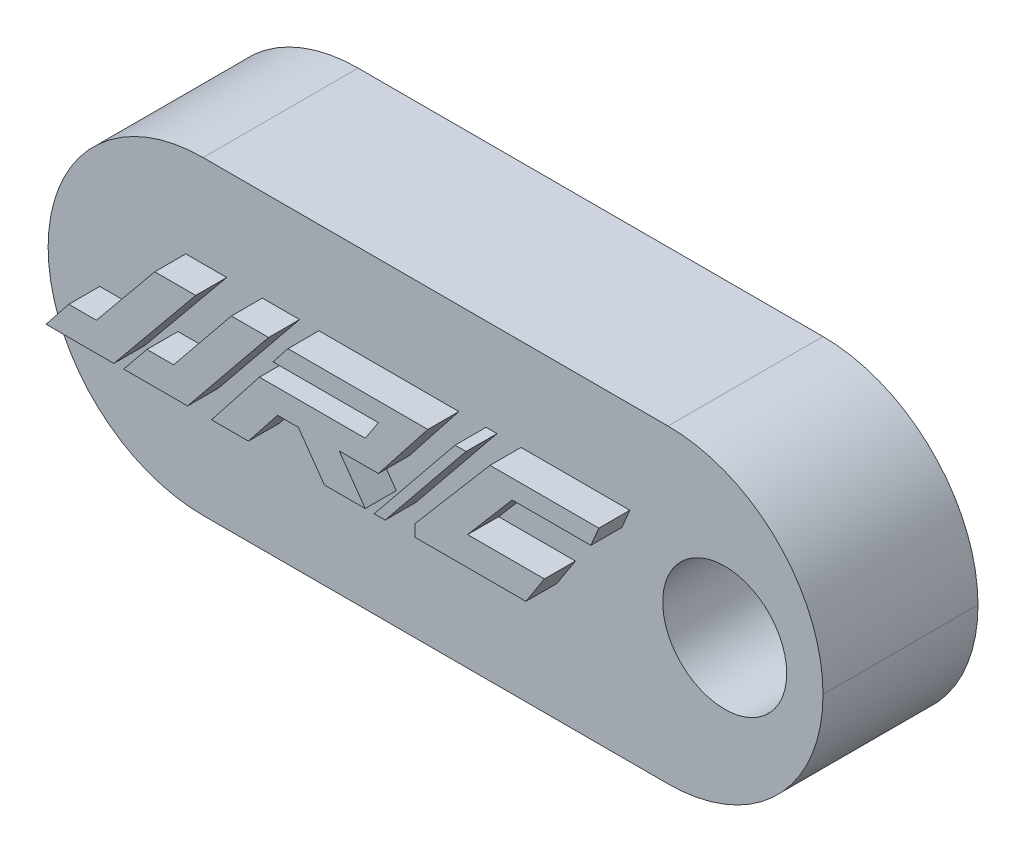
SolidWorks part; units mm, degrees
ref_plane "Plan de face" through (0, 0, 0) normal (0, 0, 1) x (1, 0, 0)
ref_plane "Plan de dessus" through (0, 0, 0) normal (0, 1, 0) x (1, 0, 0)
ref_plane "Plan de droite" through (0, 0, 0) normal (1, 0, 0) x (0, 0, -1)
sketch "Esquisse1" plane through (0, 0, 0) normal (0, 0, 1) x (1, 0, 0)
  line L1 (-25, -10) -> (25, -10)
  line L2 (-25, -10) -> (-25, 10)
  line L3 (-25, 10) -> (25, 10)
  line L4 (25, -10) -> (25, 10)
  line L5 (-25, -10) -> (25, 10) construction
  line L6 (-25, 10) -> (25, -10) construction
  point P0 (0, 0)
  dimension "D1" = 20
  dimension "D2" = 50
extrude "Boss.-Extru.1" add sketch "Esquisse1" along normal blind 10
fillet "Congé1" radius 10 4 edges at (-25, 10, 5) (25, 10, 5) (25, -10, 5) (-25, -10, 5)
sketch "Esquisse2" plane through (0, 0, 10) normal (0, 0, 1) x (1, 0, 0)
  circle A0 centre (18.6554, 0) radius 4
extrude "Enlèv. mat.-Extru.1" cut sketch "Esquisse2" against normal through all
sketch "Esquisse3" plane through (0, 0, 10) normal (0, 0, 1) x (1, 0, 0)
  line L0 (-23.1374, -2.3821) -> (-18.759, -2.3821)
  line L1 (-18.759, -2.3821) -> (-13.4772, 4.0591)
  line L2 (-13.4772, 4.0591) -> (-16.1181, 4.0591)
  line L3 (-16.1181, 4.0591) -> (-19.8842, -0.5337)
  line L4 (-19.8842, -0.5337) -> (-21.6692, -0.5337)
  line L5 (-21.6692, -0.5337) -> (-23.1374, -2.3821)
  line L6 (-18.1265, -2.3821) -> (-14.0041, -2.3821)
  line L7 (-14.0041, -2.3821) -> (-8.7745, 4.0591)
  line L8 (-18.1265, -2.3821) -> (-16.6258, -0.5337)
  line L9 (-16.6258, -0.5337) -> (-14.9059, -0.5337)
  line L10 (-14.9059, -0.5337) -> (-11.177, 4.0591)
  line L11 (-11.177, 4.0591) -> (-8.7745, 4.0591)
  line L12 (-12.4582, -2.3821) -> (-10.0749, -2.3821)
  line L13 (-12.4582, -2.3821) -> (-9.3664, 1.5471)
  line L14 (-9.3664, 1.5471) -> (-2.5386, 1.5471)
  line L15 (-10.0749, -2.3821) -> (-8.2005, 0)
  line L16 (-8.2005, 0) -> (-6.8543, 0)
  line L17 (-6.8543, 0) -> (-5.1732, -2.3821)
  line L18 (-5.1732, -2.3821) -> (-2.5386, -2.3821)
  line L19 (-2.5386, -2.3821) -> (-4.2197, 0)
  line L20 (-4.2197, 0) -> (-1.6914, 0)
  line L21 (-1.6914, 0) -> (1.5026, 4.0591)
  line L22 (1.5026, 4.0591) -> (-7.5274, 4.0591)
  line L23 (-7.5274, 4.0591) -> (-8.4872, 2.8394)
  line L24 (-8.4872, 2.8394) -> (-1.6914, 2.8394)
  line L25 (-1.6914, 2.8394) -> (-2.5386, 1.5471)
  line L26 (3.2585, 4.0591) -> (3.967, 4.0591)
  line L27 (3.967, 4.0591) -> (-1.2504, -2.3821)
  line L28 (3.2585, 4.0591) -> (-1.9589, -2.3821)
  line L29 (-1.9589, -2.3821) -> (-1.2504, -2.3821)
  line L30 (7.8318, -2.3821) -> (0.682, -2.3821)
  line L31 (0.682, -1.6092) -> (5.5129, 4.0591)
  line L32 (5.5129, 4.0591) -> (12.5339, 4.0591)
  line L33 (12.5339, 4.0591) -> (12.0186, 2.8394)
  line L34 (12.0186, 2.8394) -> (6.9441, 2.8394)
  line L35 (6.9441, 2.8394) -> (4.0694, -0.5337)
  line L36 (4.0694, -0.5337) -> (9.0234, -0.5337)
  line L37 (9.0234, -0.5337) -> (7.8318, -2.3821)
  spline S0 degree 1 poles (0.682, -2.3821) (0.682, -1.6092) knots 0 0 1 1
extrude "Boss.-Extru.2" add sketch "Esquisse3" along normal blind 2
